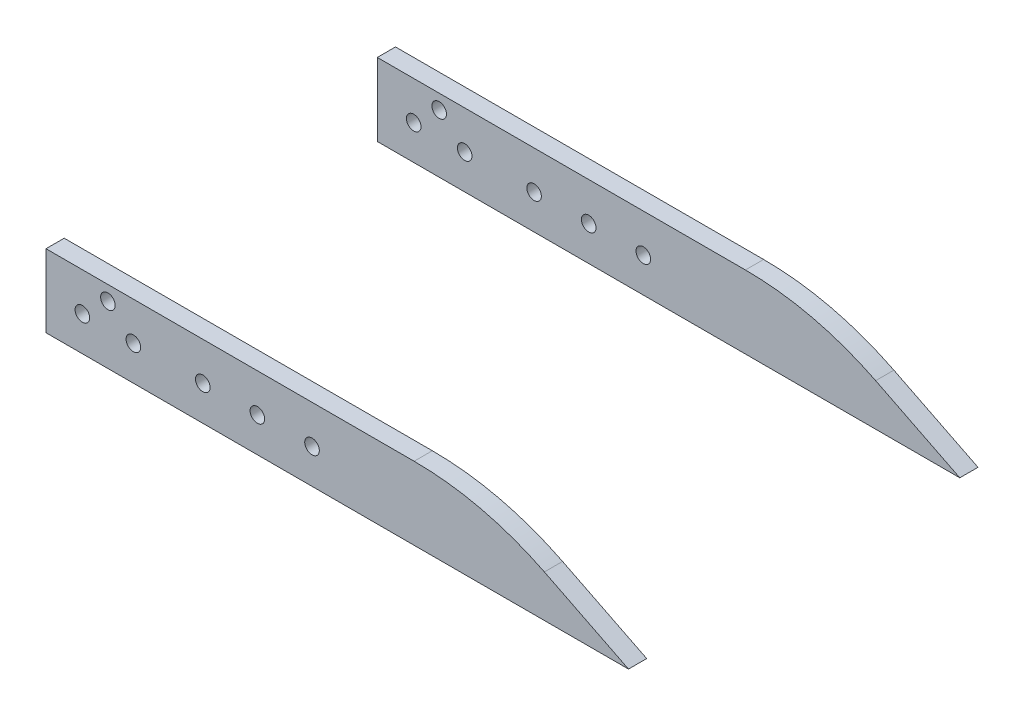
SolidWorks part; units mm, degrees
ref_plane "Front Plane" through (0, 0, 0) normal (0, 0, 1) x (1, 0, 0)
ref_plane "Top Plane" through (0, 0, 0) normal (0, 1, 0) x (1, 0, 0)
ref_plane "Right Plane" through (0, 0, 0) normal (1, 0, 0) x (0, 0, -1)
sketch "Sketch2" plane through (0, 0, 0) normal (0, 0, 1) x (1, 0, 0)
  line L0 (0, 0) -> (0, -20)
  line L1 (0, -20) -> (160, -20)
  line L2 (0, 0) -> (101.1146, 0)
  line L3 (136.8916, -8.4458) -> (160, -20)
  arc A1 (101.1146, 0) -> (136.8916, -8.4458) centre (101.1146, -80) cw
  point P12 (120, 0)
  dimension "D1" = 80
  dimension "D2" = 20
  dimension "D3" = 160
  dimension "D4" = 120
extrude "Boss-Extrude1" add sketch "Sketch2" along normal blind 5 from offset 91
extrude "Boss-Extrude2" add sketch "Sketch2<2>" along normal blind 5 separate body
sketch "Sketch2<2>" plane through (0, 0, 0) normal (0, 0, 1) x (1, 0, 0) same geometry as "Sketch2"
sketch "Sketch3" plane through (0, 0, 5) normal (0, 0, 1) x (1, 0, 0)
  line L0 (101.1146, 0) -> (0, 0) construction
  line L1 (0, 0) -> (0, -20) construction
  circle A0 centre (10, -10.5) radius 2
  circle A1 centre (17, -4) radius 2
  circle A2 centre (24, -10.5) radius 2
  circle A3 centre (43.0686, -10.5) radius 2
  circle A4 centre (58.0686, -10.5) radius 2
  circle A5 centre (73.0686, -10.5) radius 2
  point P16 (0, 0)
  point P17 (0, 0)
  dimension "D1" = 4
  dimension "D2" = 10.5
  dimension "D3" = 10
extrude "Cut-Extrude1" cut sketch "Sketch3" against normal through all both and the other way through all
